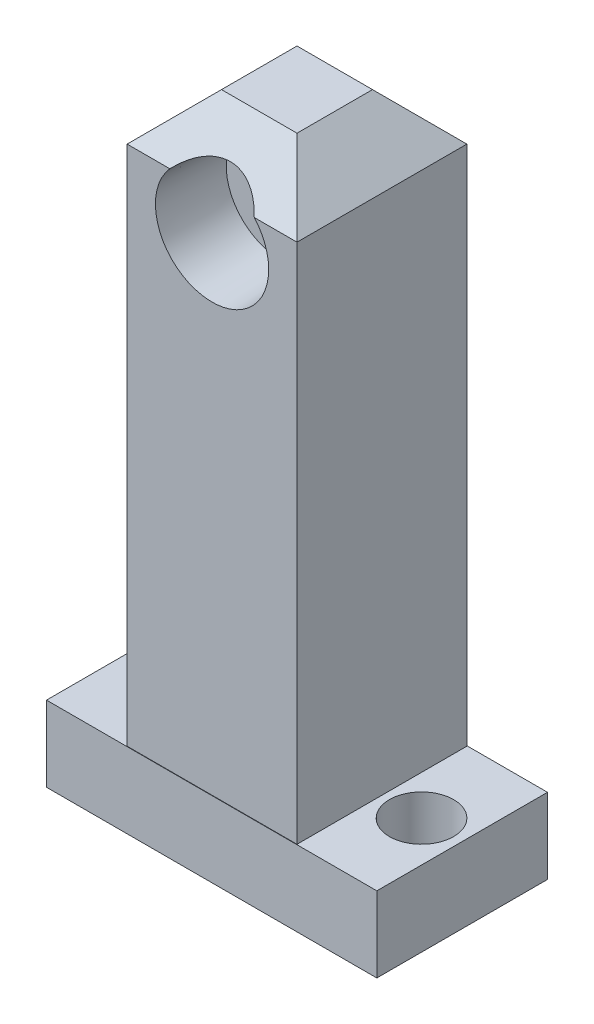
SolidWorks part; units mm, degrees
ref_plane "Front Plane" through (0, 0, 0) normal (0, 0, 1) x (1, 0, 0)
ref_plane "Top Plane" through (0, 0, 0) normal (0, 1, 0) x (1, 0, 0)
ref_plane "Right Plane" through (0, 0, 0) normal (1, 0, 0) x (0, 0, -1)
sketch "Sketch4" plane through (0, 0, 0) normal (0, 1, 0) x (1, 0, 0)
  line L1 (-9, 9) -> (9, 9)
  line L2 (-9, 9) -> (-9, -9)
  line L3 (-9, -9) -> (9, -9)
  line L4 (9, 9) -> (9, -9)
  line L5 (-9, 9) -> (9, -9) construction
  line L6 (-9, -9) -> (9, 9) construction
  point P0 (0, 0)
extrude "Boss-Extrude2" add sketch "Sketch4" along normal mid plane 18
sketch "Sketch5" plane through (0, 0, 9) normal (0, 0, 1) x (1, 0, 0)
  circle A0 centre (0, 0) radius 3.15
extrude "Cut-Extrude1" cut sketch "Sketch5" against normal blind 18 contours A0
sketch "Sketch6" plane through (0, 0, 9) normal (0, 0, 1) x (1, 0, 0)
  circle A0 centre (0, 0) radius 6
  dimension "D1" = 12
extrude "Cut-Extrude2" cut sketch "Sketch6" against normal blind 7.25 draft 2
sketch "Sketch8" plane through (0, 0, -9) normal (0, 0, -1) x (-1, 0, 0)
  circle A0 centre (0, 0) radius 6
  dimension "D1" = 12
extrude "Cut-Extrude3" cut sketch "Sketch8" against normal blind 7.25 draft 2
chamfer "Chamfer1" distance 5 angle 45 4 edges at (0, 9, 9) (-9, 9, 0) (0, 9, -9) (9, 9, 0)
sketch "Sketch13" plane through (0, -9, 0) normal (0, -1, 0) x (1, 0, 0)
  line L1 (-9, 9) -> (9, 9)
  line L2 (-9, 9) -> (-9, -9)
  line L3 (-9, -9) -> (9, -9)
  line L4 (9, 9) -> (9, -9)
  line L5 (-9, 9) -> (9, -9) construction
  line L6 (-9, -9) -> (9, 9) construction
  point P0 (0, 0)
extrude "Boss-Extrude4" add sketch "Sketch13" along normal blind 50.25
sketch "Sketch14" plane through (0, -59.25, 0) normal (0, -1, 0) x (-1, 0, 0)
  line L1 (17.5, -9.0419) -> (-17.5, -9.0419)
  line L2 (17.5, -9.0419) -> (17.5, 9.0419)
  line L3 (17.5, 9.0419) -> (-17.5, 9.0419)
  line L4 (-17.5, -9.0419) -> (-17.5, 9.0419)
  line L5 (17.5, -9.0419) -> (-17.5, 9.0419) construction
  line L6 (17.5, 9.0419) -> (-17.5, -9.0419) construction
  point P0 (0, 0)
  dimension "D1" = 39.3957
  dimension "D2" = 35
extrude "Boss-Extrude5" add sketch "Sketch14" against normal blind 8 contours L2 L3 L4 L1
sketch "Sketch15" plane through (0, -51.25, 0) normal (0, 1, 0) x (1, 0, 0)
  circle A0 centre (-13.07, 0) radius 3.4
extrude "Cut-Extrude4" cut sketch "Sketch15" against normal blind 8 contours A0
sketch "Sketch16" plane through (0, -51.25, 0) normal (0, 1, 0) x (1, 0, 0)
  circle A0 centre (13.1945, 0) radius 3.4
extrude "Cut-Extrude5" cut sketch "Sketch16" against normal blind 8
